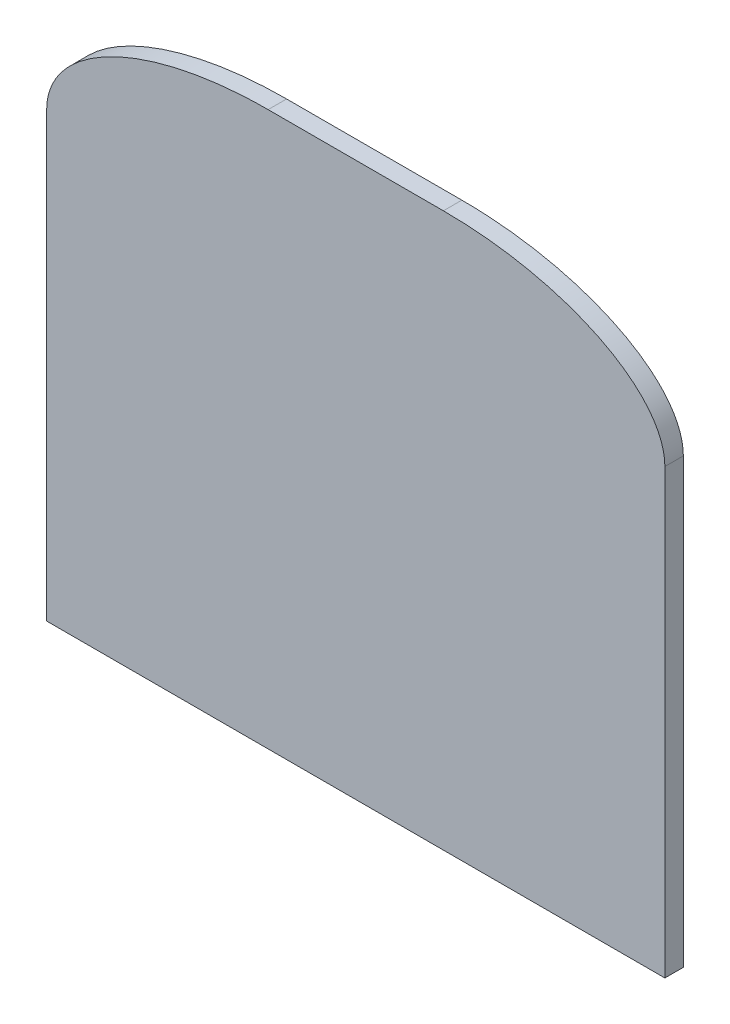
SolidWorks part; units mm, degrees
ref_plane "Front Plane" through (0, 0, 0) normal (0, 0, 1) x (1, 0, 0)
ref_plane "Top Plane" through (0, 0, 0) normal (0, 1, 0) x (1, 0, 0)
ref_plane "Right Plane" through (0, 0, 0) normal (1, 0, 0) x (0, 0, -1)
sketch "Sketch2" plane through (0, 0, 0) normal (1, 0, 0) x (0, 0, -1)
  line L0 (20.54, 22.225) -> (-292.6733, 22.225) construction
  line L1 (0, 22.225) -> (-12.7, 22.225)
  line L2 (0, 255) -> (0, 245) construction
  line L3 (0, 403.225) -> (0, 22.225)
  line L6 (-12.7, 22.225) -> (-12.7, 403.225)
  line L7 (-12.7, 403.225) -> (0, 403.225)
  dimension "D1" = 12.7
  dimension "D2" = 381
extrude "Boss-Extrude1" add sketch "Sketch2" against normal offset from surface 12.7 and the other way offset from surface (212.7 mm away) 12.7
fillet "Fillet1" radius 152.4 2 edges at (212.7, 403.225, 6.35) (-212.7, 403.225, 6.35)
